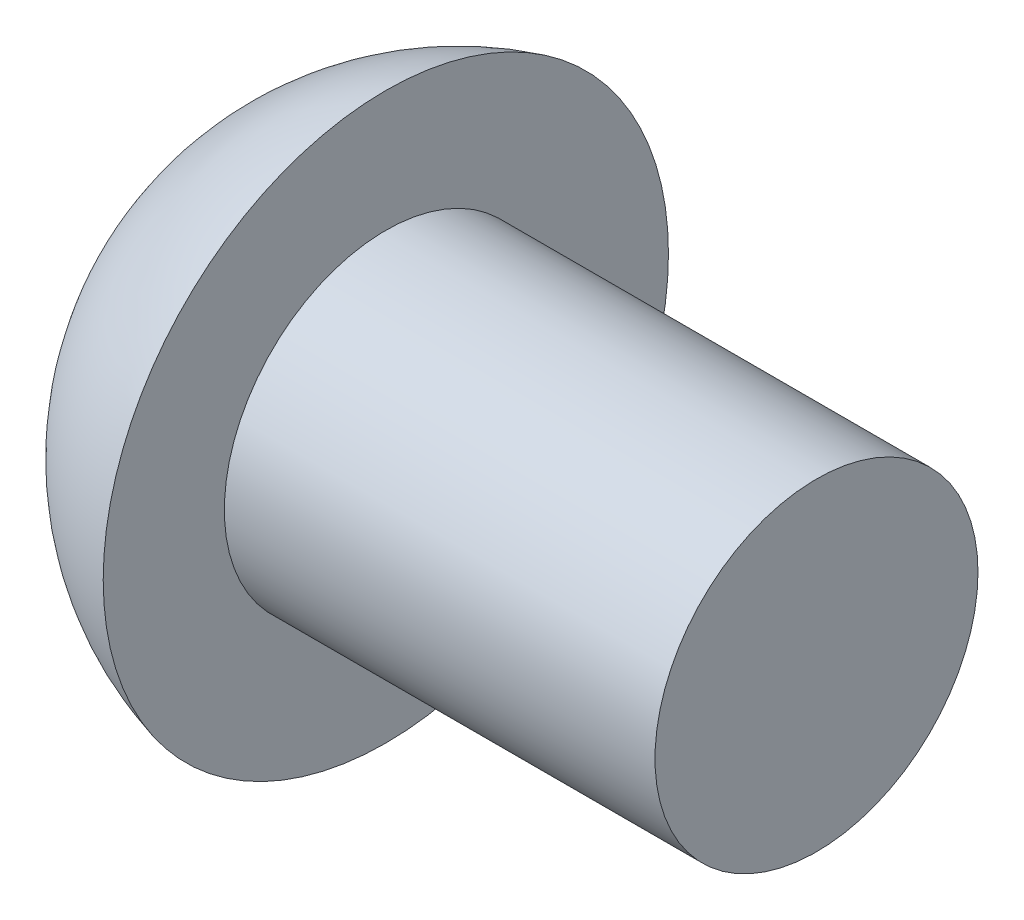
SolidWorks part; units mm, degrees
ref_plane "Front" through (0, 0, 0) normal (0, 0, 1) x (1, 0, 0)
ref_plane "Top" through (0, 0, 0) normal (0, 1, 0) x (1, 0, 0)
ref_plane "Right" through (0, 0, 0) normal (1, 0, 0) x (0, 0, -1)
sketch "Sketch1" plane through (0, 0, 0) normal (1, 0, 0) x (0, 0, -1)
  line L0 (0, 0) -> (2, 0) construction
  circle A0 centre (0, 0) radius 5.25
extrude "BaseHead" add sketch "Sketch1" along normal blind 3.3
sketch "Sketch2" plane through (3.3, 0, 0) normal (1, 0, 0) x (0, 0, -1)
  circle A0 centre (0, 0) radius 3
extrude "BaseBody" add sketch "Sketch2" along normal blind 10
cosmetic thread "ThreadCosmetic1" parameters "D1"=8, "THD_MINOR"=4.917
fillet "HeadFillet" [suppressed] radius 0.25
sketch "Sketch3" plane through (-13.4796, 2.4796, 0) normal (0, 0, 1) x (0, -1, 0)
  line L0 (2.4796, 13.4796) -> (2.4796, 41.0387) construction
  line L3 (-2.7704, 13.4796) -> (2.4796, 13.4796) construction
  line L5 (-7.7704, 16.7796) -> (-7.7704, 8.4796)
  line L6 (-0.3104, 13.4796) -> (-0.3104, 8.4796)
  line L7 (-0.3104, 8.4796) -> (-7.7704, 8.4796)
  line L8 (-7.7704, 16.7796) -> (-2.7704, 16.7796)
  line L9 (-2.7704, 13.4796) -> (7.7296, 13.4796) construction
  arc A0 (-2.7704, 16.7796) -> (-0.3104, 13.4796) centre (2.4796, 18.1263) ccw
  dimension "D2" = 5
  dimension "e" = 5.58
  dimension "D3" = 5
revolve "Cut-Revolve1" cut sketch "Sketch3" angle 360 about L0
sketch "Sketch4" plane through (0, 0, 0) normal (1, 0, 0) x (0, 0, -1)
  line L1 (2.3094, 0) -> (1.1547, 2)
  line L2 (1.1547, 2) -> (-1.1547, 2)
  line L3 (-1.1547, 2) -> (-2.3094, 0)
  line L4 (-2.3094, 0) -> (-1.1547, -2)
  line L5 (-1.1547, -2) -> (1.1547, -2)
  line L6 (1.1547, -2) -> (2.3094, 0)
  circle A0 centre (0, 0) radius 2 construction
  dimension "s" = 4
extrude "HexagonSocket" cut sketch "Sketch4" along normal blind 2.08
sketch "Sketch5" plane through (2.08, 0, 0) normal (-1, 0, 0) x (0, 0, 1)
  line L0 (1.1547, -2) -> (-1.1547, -2) construction
  line L1 (-1.1547, -2) -> (-2.3094, 0) construction
  line L2 (2.3094, 0) -> (1.1547, -2) construction
  line L3 (1.1547, 2) -> (2.3094, 0) construction
  line L4 (-2.3094, 0) -> (-1.1547, 2) construction
  line L5 (-1.1547, 2) -> (1.1547, 2) construction
  line L6 (1.1547, -2) -> (-1.1547, -2)
  line L7 (-1.1547, -2) -> (-2.3094, 0)
  line L8 (2.3094, 0) -> (1.1547, -2)
  line L9 (1.1547, 2) -> (2.3094, 0)
  line L10 (-2.3094, 0) -> (-1.1547, 2)
  line L11 (-1.1547, 2) -> (1.1547, 2)
extrude "Cut-Extrude2" cut sketch "Sketch5" against normal blind 5 draft 60
sketch "Sketch6" plane through (0, 0, 0) normal (0, 0, 1) x (1, 0, 0)
  line L0 (13.3, 2.531) -> (13.5708, 3)
  line L1 (13.5708, 3) -> (13.5708, 3.5415)
  line L2 (13.5708, 3.5415) -> (13.0292, 3.5415)
  line L3 (13.0292, 3.5415) -> (13.0292, 3)
  line L4 (13.0292, 3) -> (13.3, 2.531)
  line L5 (0, 0) -> (24.7294, 0) construction
  line L6 (13.3, -3) -> (13.3, 3) construction
  dimension "D1" = 0.5415
  dimension "D2" = 6
revolve "Cut-Revolve10" [suppressed] cut sketch "Sketch6" angle 360 about L5
pattern_linear "LPattern10" [suppressed] count 13 spacing 0.6498 along (-1, 0, 0) of bodies 106
sketch "草图1" plane through (13.3, 0, 0) normal (1, 0, 0) x (0, 0, -1)
  circle A1 centre (0, 0) radius 3
  circle A2 centre (0, 0) radius 3
  dimension "D1" = 0
extrude "切除-拉伸1" cut sketch "草图1" against normal blind 2
equation "\"D1@ThreadCosmetic1\" = \"l@BaseBody\" - \"a@Sketch1\""
equation "\"D2@Sketch6\" = \"d@Sketch2\""
equation "\"D1@Sketch6\" =  (\"d@Sketch2\" - \"THD_MINOR@ThreadCosmetic1\" )  / 2"
equation "\"D3@LPattern10\" = \"D1@Sketch6\" * 1.2"
equation "\"D1@LPattern10\" = \"D1@ThreadCosmetic1\" / \"D3@LPattern10\" + 1"
